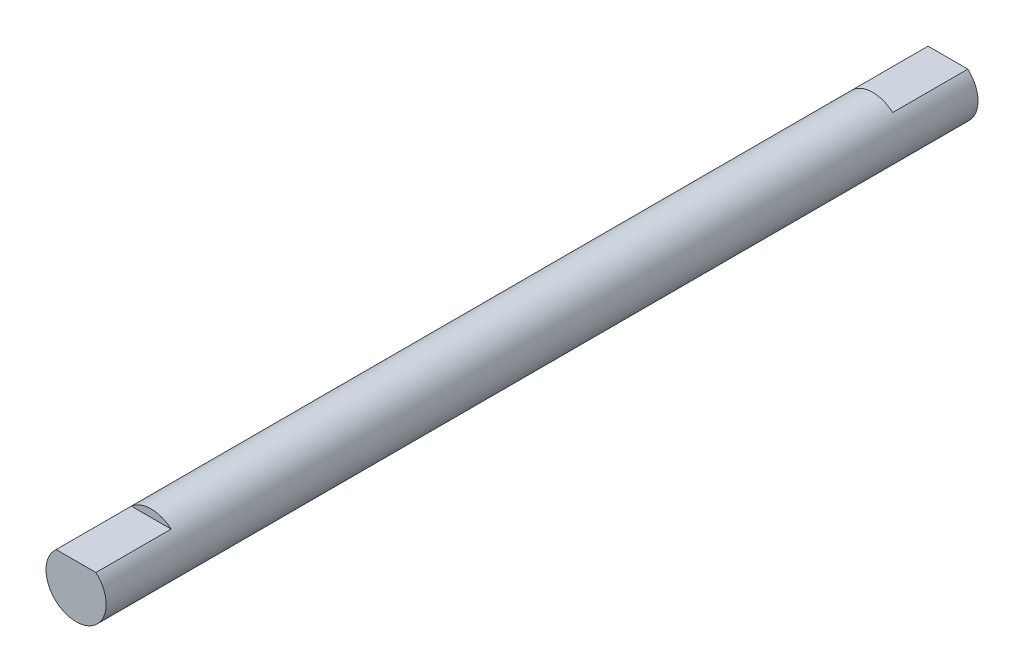
SolidWorks part; units mm, degrees
ref_plane "Plano frontal" through (0, 0, 0) normal (0, 0, 1) x (1, 0, 0)
ref_plane "Plano superior" through (0, 0, 0) normal (0, 1, 0) x (1, 0, 0)
ref_plane "Plano direito" through (0, 0, 0) normal (1, 0, 0) x (0, 0, -1)
sketch "Esboço1" plane through (0, 0, 0) normal (0, 0, 1) x (1, 0, 0)
  circle A0 centre (0, 0) radius 4
  dimension "D1" = 8
extrude "Ressalto-extrusão1" add sketch "Esboço1" along normal blind 58 and the other way blind 58
sketch "Esboço2" plane through (0, 0, 58) normal (0, 0, 1) x (1, 0, 0)
  line L0 (0, 4) -> (0, 3) construction
  line L1 (2.6458, 3) -> (-2.6458, 3)
  circle A0 centre (0, 0) radius 4 construction
  arc A1 (2.6458, 3) -> (-2.6458, 3) centre (0, 0) ccw
  dimension "D1" = 1
extrude "Corte-extrusão1" cut sketch "Esboço2" against normal blind 10
mirror "Espelhar2" about plane through (0, 0, 0) normal (0, 0, 1) of "Corte-extrusão1"
